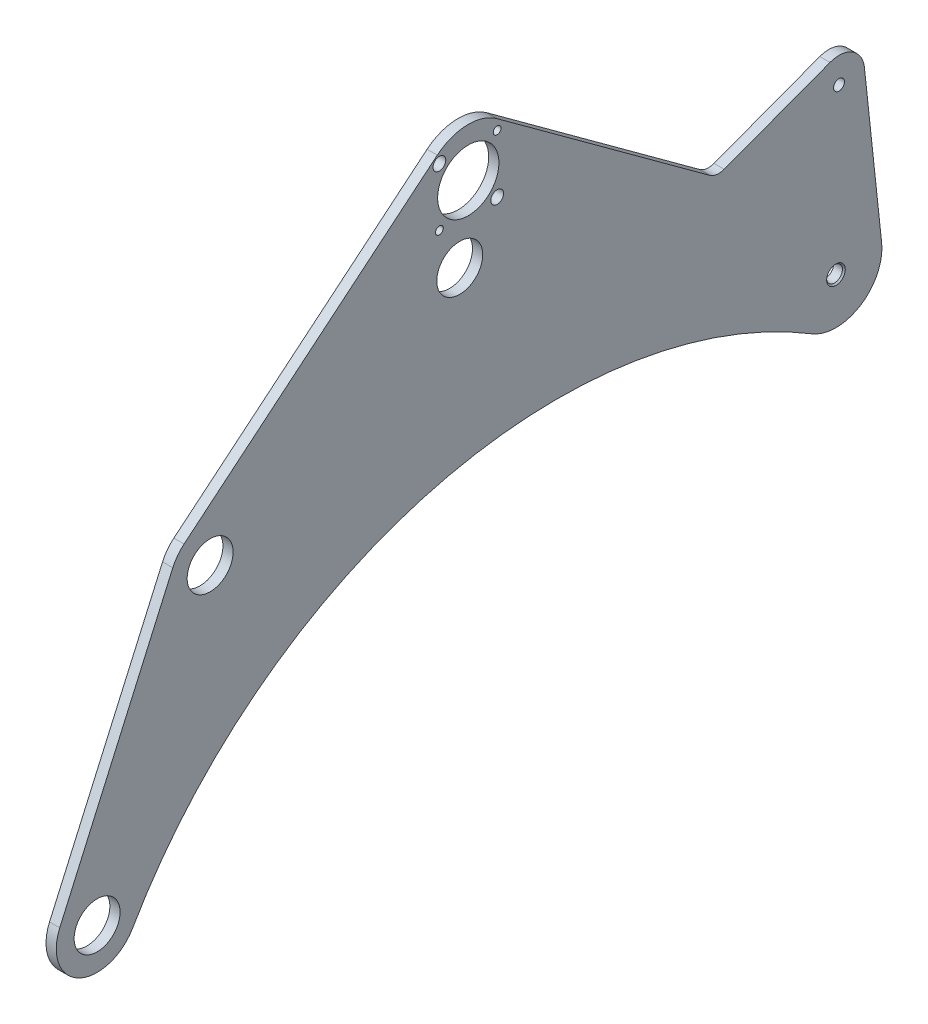
SolidWorks part; units mm, degrees
material "Acrylic (Medium-high impact)"
ref_plane "Front Plane" through (0, 0, 0) normal (0, 0, 1) x (1, 0, 0)
ref_plane "Top Plane" through (0, 0, 0) normal (0, 1, 0) x (1, 0, 0)
ref_plane "Right Plane" through (0, 0, 0) normal (1, 0, 0) x (0, 0, -1)
sketch "Sketch1" plane through (0, 0, 0) normal (1, 0, 0) x (0, 0, -1)
  line L0 (-548.7618, -304.8) -> (152.435, -304.8)
  line L1 (-192.8252, -101.6) -> (-152.4, -101.6)
  line L2 (-234.95, -143.7248) -> (-234.95, -186.4752)
  line L3 (-192.8252, -228.6) -> (-152.4, -228.6)
  line L4 (-152.4, -101.6) -> (-152.4, -228.6)
  line L10 (-476.25, -304.8) -> (-476.25, -143.7248)
  line L11 (314.7831, 139.7) -> (-192.8252, 139.7)
  line L12 (-133.3527, -63.5) -> (-641.3527, -63.5)
  circle A1 centre (0, 0) radius 6.35
  circle A6 centre (-459.3781, -120.65) radius 9.525
  circle A7 centre (-389.0971, 38.1) radius 9.525
  circle A8 centre (-233.921, 120.65) radius 9.525
  arc A9 (-234.95, -186.4752) -> (-192.8252, -228.6) centre (-192.8252, -186.4752) ccw
  arc A10 (-192.8252, -101.6) -> (-234.95, -143.7248) centre (-192.8252, -143.7248) ccw
  circle A11 centre (-159.3874, 20.4789) radius 120.65
  circle A12 centre (-228.6, 165.1) radius 29.845
  arc A23 (-192.8252, 139.7) -> (-476.25, -143.7248) centre (-192.8252, -143.7248) ccw
  circle B0 centre (-389.0971, 38.1) radius 20
  line B1 (-459.3781, -120.65) -> (-445.4292, -105.3497)
  circle B2 centre (-459.3781, -120.65) radius 20
  circle B3 centre (-233.921, 120.65) radius 20
  line B4 (-228.6, 165.1) -> (-225.2662, 181.3097)
  circle B5 centre (-228.6, 165.1) radius 20
  circle B6 centre (-603.5064, -180.5864) radius 6.35
  dimension "D1" = 12.7
  dimension "D2" = 19.05
  dimension "D3" = 42.1248
  dimension "D4" = 127
  dimension "D7" = 203.2
  dimension "D6" = 241.3
  dimension "D16" = 59.69
  dimension "D10" = 25.4
  dimension "D11" = 25.4
  dimension "D12" = 25.4
  dimension "D5" = 82.55
  dimension "D8" = 304.8
  dimension "D9" = 152.4
  dimension "D13" = 57.15
  dimension "D14" = 101.6
  dimension "D15" = 184.15
  dimension "D17" = 228.6
  dimension "D18" = 165.1
  dimension "D23" = 241.3
  dimension "D24" = 241.3
  dimension "D25" = 241.3
  dimension "D26" = 508
sketch_block_instance "Block1-1"
sketch_block "Block1" parameters "D1"=8
sketch_block_instance "Block2-1"
sketch_block "Block2" parameters "D1"=8
sketch_block_instance "Block3-1"
sketch_block "Block3" parameters "D1"=8
sketch_block_instance "Block4-1"
sketch_block "Block4" parameters "D1"=40, "D2"=8
sketch_block_instance "Block5-1"
sketch_block "Block5" parameters "D1"=8
sketch "Sketch2" plane through (0, 0, 0) normal (1, 0, 0) x (0, 0, -1)
  line L1 (-482.6038, -110.3676) -> (-412.3228, 48.3824)
  line L3 (-405.3176, 57.6462) -> (-247.8618, 188.3112)
  line L5 (-210.8028, 189.4523) -> (-78.4566, 92.7306)
  line L6 (-1064.3654, -146.05) -> (154.0419, -146.05) construction
  line L7 (-1029.8132, 195.2625) -> (188.5941, 195.2625) construction
  line L8 (17.6757, 102.9734) -> (28.4115, 3.0526)
  line L10 (-3.6748, 116.1447) -> (-69.4967, 91.5006)
  line L11 (1.8916, 101.2775) -> (0, 0) construction
  arc A0 (-405.3176, 57.6462) -> (-412.3228, 48.3824) centre (-389.0971, 38.1) ccw
  arc A2 (-482.6038, -110.3676) -> (-437.3473, -133.2913) centre (-459.3781, -120.65) ccw
  arc A4 (-210.8028, 189.4523) -> (-247.8618, 188.3112) centre (-228.6, 165.1) ccw
  arc A5 (-14.8266, -24.4275) -> (28.4115, 3.0526) centre (0, 0) ccw
  arc A8 (-437.3473, -133.2913) -> (-14.8266, -24.4275) centre (-172.9775, -284.9872) cw
  circle A12 centre (-459.3781, -120.65) radius 9.525 construction
  circle A13 centre (-389.0971, 38.1) radius 9.525 construction
  arc A14 (17.6757, 102.9734) -> (-3.6748, 116.1447) centre (1.8916, 101.2775) ccw
  arc A15 (-78.4566, 92.7306) -> (-69.4967, 91.5006) centre (-72.8365, 100.4209) ccw
  circle A17 centre (1.8916, 101.2775) radius 3.3782
  point P29 (-74.3084, 89.699)
  dimension "D1" = 25.4
  dimension "D2" = 57.15
  dimension "D3" = 60.325
  dimension "D4" = 304.8
  dimension "D6" = 1.07
  dimension "D7" = 31.75
  dimension "D8" = 76.2
  dimension "D5" = 101.2952
  dimension "D9" = 9.525
  dimension "D10" = 6.7564
extrude "Boss-Extrude1" add sketch "Sketch2" along normal blind 6.35
sketch "Sketch3" plane through (6.35, 0, 0) normal (1, 0, 0) x (0, 0, -1)
  line L0 (-210.6395, 183.0605) -> (-246.5605, 147.1395) construction
  line L1 (-228.6, 165.1) -> (-228.6, 205.0182) construction
  line L2 (-246.5605, 183.0605) -> (-210.6395, 147.1395) construction
  circle A0 centre (-233.921, 120.65) radius 14.2875
  circle A1 centre (-389.0971, 38.1) radius 14.2875
  circle A2 centre (-459.3781, -120.65) radius 14.2875
  circle A3 centre (-228.6, 165.1) radius 19.05
  circle A5 centre (-246.5605, 147.1395) radius 2.413
  circle A7 centre (-210.6395, 147.1395) radius 3.9687
  circle A8 centre (-210.6395, 183.0605) radius 2.413
  circle A9 centre (-246.5605, 183.0605) radius 3.9687
  point P18 (-228.6, 165.1)
  point P28 (-228.6, 165.1)
  dimension "D1" = 38.1
  dimension "D2" = 28.575
  dimension "D3" = 4.826
  dimension "D4" = 50.8
  dimension "D5" = 45
  dimension "D6" = 7.9375
  dimension "D7" = 50.8
extrude "Cut-Extrude1" cut sketch "Sketch3" against normal up to next
hole_wizard "3/8 Clearance Hole2" positions "Sketch7" profile "Sketch8" hole size "3/8" standard "ANSI Inch" end condition through all
sketch "Sketch7" plane through (6.35, 0, 0) normal (1, 0, 0) x (0, 0, -1)
  point P0 (0, 0)
sketch "Sketch8" plane through (6.35, 0, 0) normal (0, 1, 0) x (0, 0, -1)
  line L0 (0, 0) -> (0, 6.35)
  line L1 (0, 6.35) -> (4.9022, 6.35)
  line L2 (4.9022, 6.35) -> (4.9022, 0.8915)
  line L3 (4.9022, 0.8915) -> (5.7937, 0)
  line L5 (5.7937, 0) -> (0, 0)
  line L6 (-4.9022, 0.8915) -> (-5.7937, 0) construction
  line L11 (0, -6.35) -> (0, 107.95) construction
  dimension "Thru Hole Dia." = 9.8044
  dimension "Thru Hole Depth" = 6.35
  dimension "Near C'Sink Dia." = 11.5875
  dimension "Near C'Sink Angle" = 90
sketch "Sketch9" plane through (6.35, 0, 0) normal (1, 0, 0) x (0, 0, -1)
  line L0 (-495.9857, -146.05) -> (27.4607, -146.05) construction
  line L1 (100.4878, 195.2625) -> (-422.9585, 195.2625) construction
  arc A0 (-210.8028, 189.4523) -> (-247.8618, 188.3112) centre (-228.6, 165.1) ccw construction
  arc A1 (-482.6038, -110.3676) -> (-437.3473, -133.2913) centre (-459.3781, -120.65) ccw construction
  dimension "D1" = 341.3125
